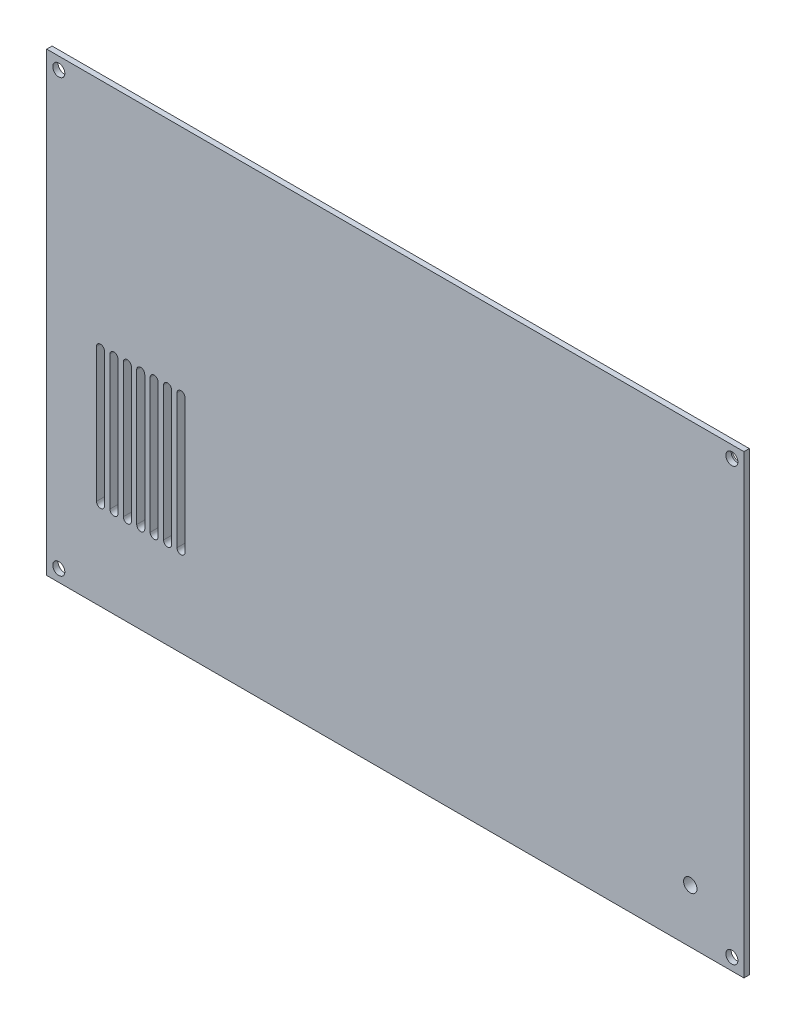
SolidWorks part; units mm, degrees
ref_plane "Front Plane" through (0, 0, 0) normal (0, 0, 1) x (1, 0, 0)
ref_plane "Top Plane" through (0, 0, 0) normal (0, 1, 0) x (1, 0, 0)
ref_plane "Right Plane" through (0, 0, 0) normal (1, 0, 0) x (0, 0, -1)
sketch "Sketch1" plane through (0, 0, 0) normal (0, 0, 1) x (1, 0, 0)
  line L4 (-130, -85) -> (130, -85)
  line L5 (130, -85) -> (130, 85)
  line L6 (130, 85) -> (-130, 85)
  line L7 (-130, 85) -> (-130, -85)
  line L8 (-130, -85) -> (130, -85)
  line L9 (130, -85) -> (130, 85)
  line L10 (130, 85) -> (-130, 85)
  line L11 (-130, 85) -> (-130, -85)
  dimension "D1" = 0
extrude "Boss-Extrude1" add sketch "Sketch1" along normal blind 2
sketch "Sketch2" plane through (0, 0, 0) normal (0, 0, -1) x (-1, 0, 0)
  line L48 (-121, 82) -> (121, 82) construction
  line L49 (-127, -76) -> (-127, 76) construction
  line L50 (-121, 82) -> (-121, 79) construction
  line L51 (-127, 76) -> (-124, 76) construction
  line L52 (-121, 82) -> (121, 82) construction
  line L53 (-127, -76) -> (-127, 76) construction
  line L54 (-121, 82) -> (-121, 79) construction
  line L55 (-127, 76) -> (-124, 76) construction
  line L56 (127, 76) -> (127, -76) construction
  line L57 (127, 76) -> (127, -76) construction
  line L58 (121, 82) -> (121, 79) construction
  line L59 (127, 76) -> (124, 76) construction
  line L60 (121, 82) -> (121, 79) construction
  line L61 (127, 76) -> (124, 76) construction
  line L62 (121, -82) -> (121, -79) construction
  line L63 (127, -76) -> (124, -76) construction
  line L64 (121, -82) -> (121, -79) construction
  line L65 (127, -76) -> (124, -76) construction
  line L66 (127, -82) -> (-127, -82) construction
  line L67 (121, -82) -> (-121, -82) construction
  line L68 (-127, -76) -> (-124, -76) construction
  line L69 (-121, -82) -> (-121, -79) construction
  line L70 (-127, -76) -> (-124, -76) construction
  line L71 (-121, -82) -> (-121, -79) construction
  line L72 (-120.492, 81.492) -> (120.492, 81.492)
  line L73 (120.492, 81.492) -> (120.492, 79)
  line L74 (126.492, 75.492) -> (124, 75.492)
  line L75 (126.492, 75.492) -> (126.492, -75.492)
  line L76 (126.492, -75.492) -> (124, -75.492)
  line L77 (120.492, -81.492) -> (120.492, -79)
  line L78 (120.492, -81.492) -> (-120.492, -81.492)
  line L79 (-120.492, -81.492) -> (-120.492, -79)
  line L80 (-126.492, -75.492) -> (-124, -75.492)
  line L81 (-126.492, -75.492) -> (-126.492, 75.492)
  line L82 (-126.492, 75.492) -> (-124, 75.492)
  line L83 (-120.492, 81.492) -> (-120.492, 79)
  arc A12 (-124, 76) -> (-121, 79) centre (-124, 79) ccw construction
  arc A13 (-124, 76) -> (-121, 79) centre (-124, 79) ccw construction
  arc A14 (121, 79) -> (124, 76) centre (124, 79) ccw construction
  arc A15 (121, 79) -> (124, 76) centre (124, 79) ccw construction
  arc A16 (124, -76) -> (121, -79) centre (124, -79) ccw construction
  arc A17 (124, -76) -> (121, -79) centre (124, -79) ccw construction
  arc A18 (-121, -79) -> (-124, -76) centre (-124, -79) ccw construction
  arc A19 (-121, -79) -> (-124, -76) centre (-124, -79) ccw construction
  arc A20 (120.492, 79) -> (124, 75.492) centre (124, 79) ccw
  arc A21 (124, -75.492) -> (120.492, -79) centre (124, -79) ccw
  arc A22 (-120.492, -79) -> (-124, -75.492) centre (-124, -79) ccw
  arc A23 (-124, 75.492) -> (-120.492, 79) centre (-124, 79) ccw
  dimension "D1" = 0.508
extrude "Boss-Extrude2" add sketch "Sketch2" along normal blind 3
sketch "Sketch3" plane through (0, 0, 2) normal (0, 0, 1) x (1, 0, 0)
  line L0 (-109.9412, -1.7697) -> (-109.9412, -51.7697) construction
  line L1 (-108.4412, -1.7697) -> (-108.4412, -51.7697)
  line L2 (-111.4412, -1.7697) -> (-111.4412, -51.7697)
  line L3 (-104.9412, -1.7697) -> (-104.9412, -51.7697) construction
  line L4 (-103.4412, -1.7697) -> (-103.4412, -51.7697)
  line L5 (-106.4412, -1.7697) -> (-106.4412, -51.7697)
  line L6 (-99.9412, -1.7697) -> (-99.9412, -51.7697) construction
  line L7 (-98.4412, -1.7697) -> (-98.4412, -51.7697)
  line L8 (-101.4412, -1.7697) -> (-101.4412, -51.7697)
  line L9 (-94.9412, -1.7697) -> (-94.9412, -51.7697) construction
  line L10 (-93.4412, -1.7697) -> (-93.4412, -51.7697)
  line L11 (-96.4412, -1.7697) -> (-96.4412, -51.7697)
  line L12 (-89.9412, -1.7697) -> (-89.9412, -51.7697) construction
  line L13 (-88.4412, -1.7697) -> (-88.4412, -51.7697)
  line L14 (-91.4412, -1.7697) -> (-91.4412, -51.7697)
  line L15 (-84.9412, -1.7697) -> (-84.9412, -51.7697) construction
  line L16 (-83.4412, -1.7697) -> (-83.4412, -51.7697)
  line L17 (-86.4412, -1.7697) -> (-86.4412, -51.7697)
  line L18 (-79.9412, -1.7697) -> (-79.9412, -51.7697) construction
  line L19 (-78.4412, -1.7697) -> (-78.4412, -51.7697)
  line L20 (-81.4412, -1.7697) -> (-81.4412, -51.7697)
  arc A0 (-108.4412, -1.7697) -> (-111.4412, -1.7697) centre (-109.9412, -1.7697) ccw
  arc A1 (-111.4412, -51.7697) -> (-108.4412, -51.7697) centre (-109.9412, -51.7697) ccw
  arc A2 (-103.4412, -1.7697) -> (-106.4412, -1.7697) centre (-104.9412, -1.7697) ccw
  arc A3 (-106.4412, -51.7697) -> (-103.4412, -51.7697) centre (-104.9412, -51.7697) ccw
  arc A4 (-98.4412, -1.7697) -> (-101.4412, -1.7697) centre (-99.9412, -1.7697) ccw
  arc A5 (-101.4412, -51.7697) -> (-98.4412, -51.7697) centre (-99.9412, -51.7697) ccw
  arc A6 (-93.4412, -1.7697) -> (-96.4412, -1.7697) centre (-94.9412, -1.7697) ccw
  arc A7 (-96.4412, -51.7697) -> (-93.4412, -51.7697) centre (-94.9412, -51.7697) ccw
  arc A8 (-88.4412, -1.7697) -> (-91.4412, -1.7697) centre (-89.9412, -1.7697) ccw
  arc A9 (-91.4412, -51.7697) -> (-88.4412, -51.7697) centre (-89.9412, -51.7697) ccw
  arc A10 (-83.4412, -1.7697) -> (-86.4412, -1.7697) centre (-84.9412, -1.7697) ccw
  arc A11 (-86.4412, -51.7697) -> (-83.4412, -51.7697) centre (-84.9412, -51.7697) ccw
  arc A12 (-78.4412, -1.7697) -> (-81.4412, -1.7697) centre (-79.9412, -1.7697) ccw
  arc A13 (-81.4412, -51.7697) -> (-78.4412, -51.7697) centre (-79.9412, -51.7697) ccw
  point P2 (-109.9412, -26.7697)
  point P10 (-104.9412, -26.7697)
  point P17 (-99.9412, -26.7697)
  point P24 (-94.9412, -26.7697)
  point P31 (-89.9412, -26.7697)
  point P38 (-84.9412, -26.7697)
  point P45 (-79.9412, -26.7697)
  dimension "D1" = 3
  dimension "D2" = 50
  dimension "D4" = 5
  dimension "D3" = 7
extrude "Cut-Extrude1" cut sketch "Sketch3" against normal through all
sketch "Sketch4" plane through (0, 0, 2) normal (0, 0, 1) x (1, 0, 0)
  line L0 (130, -85) -> (130, 85) construction
  line L1 (-130, -85) -> (130, -85) construction
  circle A0 centre (110, -65) radius 2.5
  dimension "D1" = 5
  dimension "D2" = 20
  dimension "D3" = 20
extrude "Cut-Extrude2" cut sketch "Sketch4" against normal through all contours A0
sketch "Sketch6" plane through (0, 0, 2) normal (0, 0, 1) x (1, 0, 0)
  circle A8 centre (-125.5, -80.5) radius 2.25
  circle A9 centre (-125.5, 80.5) radius 2.25
  circle A10 centre (125.5, 80.5) radius 2.25
  circle A11 centre (125.5, -80.5) radius 2.25
  circle A12 centre (125.5, 80.5) radius 2.8067 construction
  circle A13 centre (-125.5, 80.5) radius 2.8067 construction
  circle A14 centre (125.5, 80.5) radius 2.8067 construction
  circle A15 centre (-125.5, 80.5) radius 2.8067 construction
  circle A16 centre (-125.5, -80.5) radius 2.8067 construction
  circle A17 centre (-125.5, -80.5) radius 2.8067 construction
  circle A18 centre (125.5, -80.5) radius 2.8067 construction
  circle A19 centre (125.5, -80.5) radius 2.8067 construction
  dimension "D1" = 4.5
extrude "Cut-Extrude3" cut sketch "Sketch6" against normal up to next
sketch "Sketch8" plane through (0, 0, -3) normal (0, 0, -1) x (-1, 0, 0)
  line L0 (-10, -55) -> (-10, -35)
  line L1 (-60, -55) -> (-54, -55)
  line L2 (-60, -55) -> (-60, -35)
  line L3 (-60, -35) -> (-54, -35)
  line L4 (-54, -55) -> (-54, -35)
  line L13 (130, -85) -> (-130, -85) construction
  line L14 (-130, -85) -> (-130, 85) construction
  line L15 (-10, -35) -> (-4, -35)
  line L16 (-4, -55) -> (-4, -35)
  line L17 (-10, -55) -> (-4, -55)
  line L18 (40, -55) -> (40, -35)
  line L19 (40, -35) -> (46, -35)
  line L20 (46, -55) -> (46, -35)
  line L21 (40, -55) -> (46, -55)
  dimension "D1" = 6
  dimension "D2" = 30
  dimension "D3" = 20
  dimension "D4" = 70
  dimension "D6" = 50
  dimension "D5" = 3
extrude "Boss-Extrude3" [suppressed] add sketch "Sketch8" along normal blind 20
sketch "Sketch9" [suppressed] plane through (60, 0, 0) normal (1, 0, 0) x (0, 0, -1)
  line L0 (23, -35) -> (3, -35) construction
  line L2 (23, -55) -> (3, -55) construction
  line L3 (13, -35) -> (11, -35) construction
  line L4 (13, -40) -> (11, -40)
  line L5 (3, -35) -> (3, -55)
  line L6 (3, -55) -> (23, -55)
  line L7 (23, -55) -> (23, -35)
  line L8 (23, -35) -> (3, -35)
  line L9 (3, -35) -> (3, -50)
  line L10 (13, -55) -> (23, -55)
  line L11 (23, -55) -> (23, -35)
  line L12 (23, -35) -> (3, -35)
  line L13 (11, -40) -> (11, -35)
  line L14 (13, -50) -> (3, -50)
  line L15 (11, -35) -> (13, -35)
  arc A0 (13, -55) -> (13, -35) centre (13, -45) ccw
  arc A1 (13, -50) -> (13, -40) centre (13, -45) ccw
  line M7 (3, -35) -> (3, -55)
  line M8 (3, -55) -> (23, -55)
  line M9 (23, -55) -> (23, -35)
  line M10 (23, -35) -> (3, -35)
  dimension "D3" = 8
  dimension "D1" = 0
  dimension "D2" = 5
extrude "Cut-Extrude4" [suppressed] cut sketch "Sketch9" against normal through all contours L14 A1 L4 L13 L12 M7 | A0 L11 M10 | A0 M8 M9
sketch "Sketch11" plane through (0, 81.492, 0) normal (0, 1, 0) x (1, 0, 0)
  line L0 (-115, 3) -> (-115, 13)
  line L1 (-120.492, 3) -> (120.492, 3) construction
  line L2 (-95, 13) -> (-95, 11)
  line L4 (-111, 3) -> (-111, 13)
  line L6 (-99, 11) -> (-95, 11)
  line L7 (-99, 11) -> (-99, 13)
  line L8 (-111, 3) -> (-115, 3)
  line L9 (-130, -2) -> (-130, 0) construction
  line L10 (-95, 11) -> (-100.021, 7.2343) construction
  line L11 (-99, 13) -> (-99, 13) construction
  line L12 (-99, 13) -> (-102.421, 10.4343) construction
  arc A0 (-115, 13) -> (-95, 13) centre (-105, 13) cw
  arc A1 (-111, 13) -> (-99, 13) centre (-105, 13) cw
  point P16 (-105, 23)
  line M3 (120.492, 3) -> (-120.492, 3)
  dimension "D2" = 8
  dimension "D3" = 20
  dimension "D4" = 20
  dimension "D5" = 15
  dimension "D1" = 4
extrude "Boss-Extrude4" [suppressed] add sketch "Sketch11" against normal blind 6 from offset 30 contours L4 A1 L7 L6 L2 A0 L0 M3 offset against normal yes
